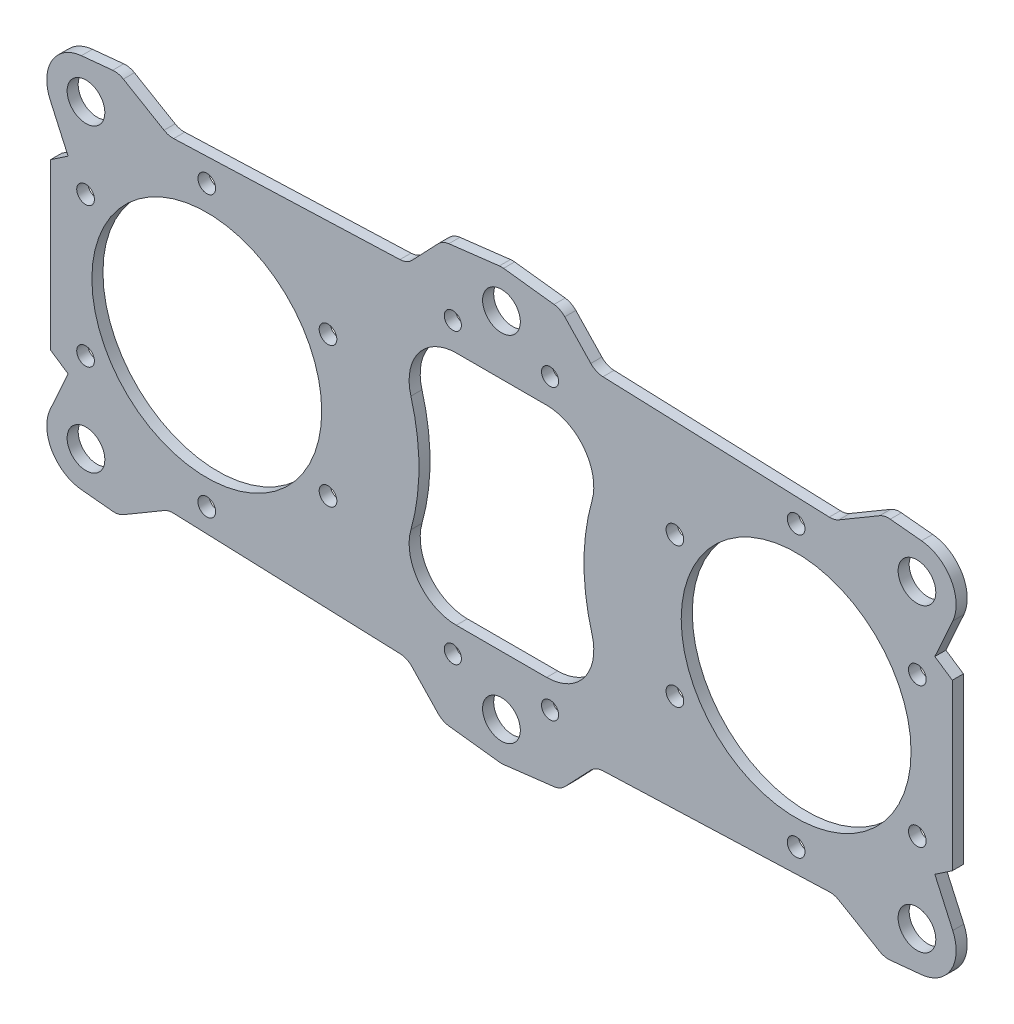
SolidWorks part; units mm, degrees
material "AISI 304"
ref_plane "Front Plane" through (0, 0, 0) normal (0, 0, 1) x (1, 0, 0)
ref_plane "Top Plane" through (0, 0, 0) normal (0, 1, 0) x (1, 0, 0)
ref_plane "Right Plane" through (0, 0, 0) normal (1, 0, 0) x (0, 0, -1)
sketch "Sketch1" plane through (0, 0, 0) normal (0, 0, 1) x (1, 0, 0)
  line L0 (0, 36.5) -> (-10, 35.3071)
  line L1 (-10, 35.3071) -> (-16, 29)
  line L2 (-16, 29) -> (-56.5, 27.5)
  line L3 (-56.5, 27.5) -> (-76.5, 14)
  line L4 (-76.5, 14) -> (-76.5, -14)
  line L5 (-87.0431, 0) -> (20.0163, 0) construction
  line L6 (0, 32.2788) -> (0, 0) construction
  line L7 (76.5, 14) -> (76.5, -14)
  line L8 (56.5, 27.5) -> (76.5, 14)
  line L9 (16, 29) -> (56.5, 27.5)
  line L10 (10, 35.3071) -> (16, 29)
  line L11 (0, 36.5) -> (10, 35.3071)
  line L12 (0, -36.5) -> (10, -35.3071)
  line L13 (10, -35.3071) -> (16, -29)
  line L14 (16, -29) -> (56.5, -27.5)
  line L15 (56.5, -27.5) -> (76.5, -14)
  line L16 (-56.5, -27.5) -> (-76.5, -14)
  line L17 (-16, -29) -> (-56.5, -27.5)
  line L18 (-10, -35.3071) -> (-16, -29)
  line L19 (0, -36.5) -> (-10, -35.3071)
  circle A0 centre (0, 30) radius 3.2
  circle A1 centre (-50, 0) radius 19.5
  circle A2 centre (50, 0) radius 19.5
  circle A3 centre (0, -30) radius 3.2
  point P35 (76.5, 0)
  point P36 (-76.5, 0)
  dimension "D1" = 6.4
  dimension "D2" = 39
  dimension "D3" = 60
  dimension "D4" = 100
  dimension "D5" = 153
  dimension "D6" = 73
  dimension "D7" = 28
  dimension "D8" = 55
  dimension "D9" = 20
  dimension "D10" = 32
  dimension "D11" = 20
  dimension "D12" = 58
extrude "Boss-Extrude1" add sketch "Sketch1" along normal blind 1.8796
sketch "Sketch2" plane through (0, 0, 1.8796) normal (0, 0, 1) x (1, 0, 0)
  line L0 (0, 49.1184) -> (0, -46.5606) construction
  line L5 (-20.0667, 20) -> (20.0667, 20)
  line L6 (0, 0) -> (-45.6375, 0) construction
  line L7 (-20.0667, -20) -> (20.0667, -20)
  arc A6 (-20.0667, -20) -> (-20.0667, 20) centre (-50, 0) ccw
  arc A7 (20.0667, -20) -> (20.0667, 20) centre (50, 0) cw
  point P12 (0, 20)
  dimension "D1" = 36
  dimension "D2" = 40
extrude "Cut-Extrude1" cut sketch "Sketch2" against normal through all
sketch "Sketch3" plane through (0, 0, 1.8796) normal (0, 0, 1) x (1, 0, 0)
  line L0 (-56.5, 27.5) -> (-65, 32.5)
  line L1 (-56.5, 27.5) -> (-76.5, 14) construction
  line L2 (-65, 32.5) -> (-80.3, 31)
  line L3 (-80.3, 31) -> (-73.537, 16)
  line L4 (-73.537, 16) -> (-56.5, 27.5)
  line L5 (0, 0) -> (0, 46.5274) construction
  line L6 (73.537, 16) -> (56.5, 27.5)
  line L7 (80.3, 31) -> (73.537, 16)
  line L8 (65, 32.5) -> (80.3, 31)
  line L9 (56.5, 27.5) -> (65, 32.5)
  line L10 (0, 0) -> (-26.0239, 0) construction
  line L11 (56.5, -27.5) -> (65, -32.5)
  line L12 (65, -32.5) -> (80.3, -31)
  line L13 (80.3, -31) -> (73.537, -16)
  line L14 (73.537, -16) -> (56.5, -27.5)
  line L15 (-73.537, -16) -> (-56.5, -27.5)
  line L16 (-80.3, -31) -> (-73.537, -16)
  line L17 (-65, -32.5) -> (-80.3, -31)
  line L18 (-56.5, -27.5) -> (-65, -32.5)
  line L19 (-16, 29) -> (-56.5, 27.5) construction
  circle A0 centre (-70.5, 25.5) radius 3.2
  circle A1 centre (70.5, 25.5) radius 3.2
  circle A2 centre (-70.5, -25.5) radius 3.2
  circle A3 centre (70.5, -25.5) radius 3.2
  dimension "D1" = 6.4
  dimension "D2" = 70.5
  dimension "D3" = 25.5
  dimension "D4" = 62
  dimension "D5" = 65
  dimension "D6" = 65
  dimension "D7" = 80.3
  dimension "D8" = 32
extrude "Boss-Extrude2" add sketch "Sketch3" against normal up to surface (1.8796 mm away) up to face at (0, 0, 0)
fillet "Fillet1" radius 6.5 4 edges at (-80.3, 31, 0.9398) (-80.3, -31, 0.9398) (80.3, -31, 0.9398) (80.3, 31, 0.9398)
sketch "Sketch4" plane through (0, 0, 1.8796) normal (0, 0, 1) x (1, 0, 0)
  line L0 (0, 48.5627) -> (0, -47.8194) construction
  circle A0 centre (-50, 0) radius 23.75 construction
  circle A1 centre (-50, 23.75) radius 1.5
  circle A2 centre (-70.5681, 11.875) radius 1.5
  circle A3 centre (-70.5681, -11.875) radius 1.5
  circle A4 centre (-50, -23.75) radius 1.5
  circle A5 centre (-29.4319, -11.875) radius 1.5
  circle A6 centre (-29.4319, 11.875) radius 1.5
  circle A7 centre (29.4319, 11.875) radius 1.5
  circle A8 centre (29.4319, -11.875) radius 1.5
  circle A9 centre (50, -23.75) radius 1.5
  circle A10 centre (70.5681, -11.875) radius 1.5
  circle A11 centre (70.5681, 11.875) radius 1.5
  circle A12 centre (50, 23.75) radius 1.5
  point P21 (-50, 0)
  point P31 (50, 0)
  dimension "D1" = 47.5
  dimension "D3" = 3
  dimension "D2" = 6
extrude "Cut-Extrude2" cut sketch "Sketch4" against normal through all
fillet "Fillet2" radius 8 4 edges at (-20.0667, -20, 0.9398) (20.0667, -20, 0.9398) (20.0667, 20, 0.9398) (-20.0667, 20, 0.9398)
sketch "Sketch6" plane through (0, 0, 0) normal (0, 0, -1) x (-1, 0, 0)
  circle A0 centre (8.25, 24.5) radius 1.45
  circle A1 centre (-8.25, 24.5) radius 1.45
  circle A2 centre (-8.25, -24.5) radius 1.45
  circle A3 centre (8.25, -24.5) radius 1.45
  dimension "D1" = 2.9
extrude "Cut-Extrude4" cut sketch "Sketch6" against normal through all
fillet "Fillet3" radius 3 18 edges at (-10, 35.3071, 0.9398) (-56.5, 27.5, 0.9398) (-16, 29, 0.9398) (-65, 32.5, 0.9398) (65, -32.5, 0.9398) (56.5, -27.5, 0.9398) (16, -29, 0.9398) (10, -35.3071, 0.9398) (0, -36.5, 0.9398) (-10, -35.3071, 0.9398) (-16, -29, 0.9398) (-65, -32.5, 0.9398) (-56.5, -27.5, 0.9398) (65, 32.5, 0.9398) (56.5, 27.5, 0.9398) (16, 29, 0.9398) (10, 35.3071, 0.9398) (0, 36.5, 0.9398)
